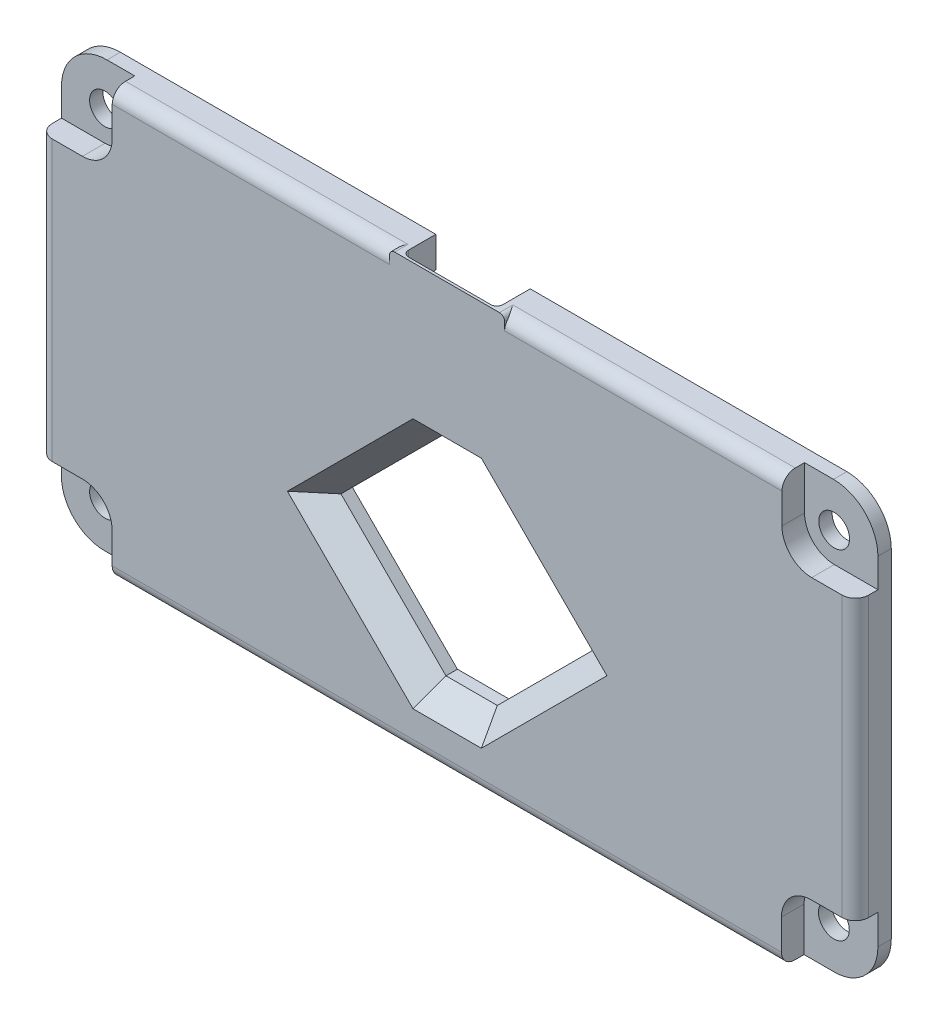
SolidWorks part; units mm, degrees
ref_plane "前视基准面" through (0, 0, 0) normal (0, 0, 1) x (1, 0, 0)
ref_plane "上视基准面" through (0, 0, 0) normal (0, 1, 0) x (1, 0, 0)
ref_plane "右视基准面" through (0, 0, 0) normal (1, 0, 0) x (0, 0, -1)
other "Configuration Table"
sketch "草图1" plane through (0, 0, 0) normal (0, 0, 1) x (1, 0, 0)
  line L0 (-73.6757, 40.1224) -> (-2.9366, 40.1224) construction
  line L1 (1.3873, 35.7985) -> (1.3873, 2.8575) construction
  line L2 (-2.8575, -1.3873) -> (-73.9297, -1.3873) construction
  line L3 (-78.111, 2.794) -> (-78.111, 35.6871) construction
  line L4 (-73.6757, 40.1224) -> (-43.4611, 40.1224)
  line L5 (1.3873, 35.7985) -> (1.3873, 2.8575)
  line L6 (-2.8575, -1.3873) -> (-73.9297, -1.3873)
  line L7 (-78.111, 2.794) -> (-78.111, 35.6871)
  line L8 (-38.3541, 24.0892) -> (-38.3541, 5.5516) construction
  line L9 (-6.6127, 15.1224) -> (-20.6127, 15.1224)
  line L10 (-6.6127, 15.1224) -> (-6.6127, 39.1224)
  line L11 (-6.6127, 39.1224) -> (-20.6127, 39.1224)
  line L12 (-20.6127, 15.1224) -> (-20.6127, 39.1224)
  line L13 (-56.111, 39.1224) -> (-70.111, 39.1224)
  line L14 (-56.111, 39.1224) -> (-56.111, 15.1224)
  line L15 (-56.111, 15.1224) -> (-70.111, 15.1224)
  line L16 (-70.111, 39.1224) -> (-70.111, 15.1224)
  line L17 (-38.2287, 24.0892) -> (-38.4795, 24.0892) construction
  line L18 (-38.6562, 5.5516) -> (-38.0519, 5.5516) construction
  line L19 (-47.9069, 14.732) -> (-28.8012, 14.732) construction
  line L20 (-47.9069, 14.6067) -> (-47.9069, 14.8574) construction
  line L21 (-28.8012, 14.8574) -> (-28.8012, 14.6067) construction
  line L22 (-38.3541, 14.732) -> (-44.9692, 8.1169) construction
  line L23 (-44.9692, 8.1169) -> (-48.3162, 4.7699) construction
  line L24 (-38.3541, 27.46) -> (-51.082, 14.732)
  line L25 (-38.3541, 27.46) -> (-25.6262, 14.732)
  line L26 (-51.082, 14.732) -> (-38.3541, 2.0041)
  line L27 (-25.6262, 14.732) -> (-38.3541, 2.0041)
  line L28 (-38.3541, 27.46) -> (-38.3541, 2.0041) construction
  line L29 (-51.082, 14.732) -> (-25.6262, 14.732) construction
  line L30 (-42.9611, 38.7041) -> (-42.9611, 36.9452) construction
  line L32 (-43.4611, 40.1224) -> (-43.4611, 30.1224)
  line L33 (-43.4611, 30.1224) -> (-33.2671, 30.1224)
  line L34 (-33.2671, 40.1224) -> (-33.2671, 30.1224)
  line L35 (-33.7671, 36.9452) -> (-33.7671, 38.7041) construction
  line L36 (-33.2671, 40.1224) -> (-2.9366, 40.1224)
  circle A0 centre (-73.8718, 35.8941) radius 1.5 construction
  circle A1 centre (-73.8718, 35.8941) radius 1.5
  circle A2 centre (-73.8718, 2.882) radius 1.5 construction
  circle A3 centre (-73.8718, 2.882) radius 1.5
  circle A4 centre (-2.9024, 2.882) radius 1.5 construction
  circle A5 centre (-2.9024, 2.882) radius 1.5
  circle A6 centre (-2.8731, 35.8776) radius 1.5 construction
  circle A7 centre (-2.8731, 35.8776) radius 1.5
  arc A8 (1.3873, 35.7985) -> (-2.9366, 40.1224) centre (-2.9366, 35.7985) ccw construction
  arc A9 (-2.8575, -1.3873) -> (1.3873, 2.8575) centre (-2.8575, 2.8575) ccw construction
  arc A10 (-78.111, 2.794) -> (-73.9297, -1.3873) centre (-73.9297, 2.794) ccw construction
  arc A11 (-73.6757, 40.1224) -> (-78.111, 35.6871) centre (-73.6757, 35.6871) ccw construction
  arc A12 (1.3873, 35.7985) -> (-2.9366, 40.1224) centre (-2.9366, 35.7985) ccw
  arc A13 (-2.8575, -1.3873) -> (1.3873, 2.8575) centre (-2.8575, 2.8575) ccw
  arc A14 (-78.111, 2.794) -> (-73.9297, -1.3873) centre (-73.9297, 2.794) ccw
  arc A15 (-73.6757, 40.1224) -> (-78.111, 35.6871) centre (-73.6757, 35.6871) ccw
  dimension "D1" = 8
  dimension "D2" = 8
  dimension "D3" = 1
  dimension "D4" = 1
  dimension "D5" = 14
  dimension "D6" = 14
  dimension "D7" = 24
  dimension "D8" = 18
  dimension "D9" = 18
  dimension "D10" = 0.5
  dimension "D11" = 0.5
  dimension "D12" = 10
extrude "凸台-拉伸1" add sketch "草图1" along normal blind 3.5
sketch "草图2" plane through (0, 0, 3.5) normal (0, 0, 1) x (1, 0, 0)
  line L1 (-20.6127, 39.1224) -> (-6.6127, 39.1224)
  line L2 (-20.6127, 39.1224) -> (-20.6127, 15.1224)
  line L3 (-20.6127, 15.1224) -> (-6.6127, 15.1224)
  line L4 (-6.6127, 39.1224) -> (-6.6127, 15.1224)
  line L5 (-70.111, 39.1224) -> (-56.111, 39.1224)
  line L6 (-70.111, 39.1224) -> (-70.111, 15.1224)
  line L7 (-70.111, 15.1224) -> (-56.111, 15.1224)
  line L8 (-56.111, 39.1224) -> (-56.111, 15.1224)
extrude "凸台-拉伸2" add sketch "草图2" against normal blind 0.5
sketch "草图3" plane through (0, 0, 3.5) normal (0, 0, 1) x (1, 0, 0)
  line L0 (-38.3541, 27.46) -> (-40.8541, 24.96)
  line L1 (-38.3541, 27.46) -> (-51.082, 14.732) construction
  line L2 (-40.8541, 24.96) -> (-35.8541, 24.96)
  line L3 (-25.6262, 14.732) -> (-38.3541, 27.46) construction
  line L4 (-35.8541, 24.96) -> (-38.3541, 27.46)
  line L5 (-38.3541, 2.0041) -> (-40.8541, 4.5041)
  line L6 (-51.082, 14.732) -> (-38.3541, 2.0041) construction
  line L7 (-40.8541, 4.5041) -> (-35.8541, 4.5041)
  line L8 (-38.3541, 2.0041) -> (-25.6262, 14.732) construction
  line L9 (-35.8541, 4.5041) -> (-38.3541, 2.0041)
  dimension "D1" = 2.5
  dimension "D2" = 45
  dimension "D3" = 2.5
extrude "凸台-拉伸3" add sketch "草图3" against normal blind 3.5
chamfer "倒角2" distance 2 angle 50 6 edges at (-30.7401, 9.6181, 3.5) (-38.3541, 4.5041, 3.5) (-45.968, 9.6181, 3.5) (-30.7401, 19.846, 3.5) (-38.3541, 24.96, 3.5) (-45.968, 19.846, 3.5) first distance on face at (-1.4024, 2.882, 3.5)
sketch "草图4" plane through (0, 30.1224, 0) normal (0, 1, 0) x (1, 0, 0)
  line L0 (-33.2671, -0.5) -> (-33.7671, -0.5)
  line L1 (-33.2671, -3.5) -> (-33.2671, 0) construction
  line L2 (-33.7671, -0.5) -> (-33.7671, -2.6525)
  line L3 (-34.3646, -3.25) -> (-42.3636, -3.25)
  line L4 (-42.9611, -2.6525) -> (-42.9611, -0.5)
  line L5 (-42.9611, -0.5) -> (-43.4611, -0.5)
  line L6 (-43.4611, -3.5) -> (-43.4611, 0) construction
  line L7 (-43.4611, -0.5) -> (-43.4611, -3.5)
  line L8 (-43.4611, -3.5) -> (-33.2671, -3.5)
  line L9 (-33.2671, -3.5) -> (-33.2671, -0.5)
  arc A0 (-33.7671, -2.6525) -> (-34.3646, -3.25) centre (-34.3646, -2.6525) cw
  arc A1 (-42.3636, -3.25) -> (-42.9611, -2.6525) centre (-42.3636, -2.6525) cw
  dimension "D1" = 0.25
  dimension "D2" = 0.5
  dimension "D3" = 0.5
  dimension "D4" = 3
  dimension "D5" = 3
extrude "凸台-拉伸4" add sketch "草图4" along normal up to surface (10 mm away) up to face at (-18.1018, 40.1224, 1.75)
sketch "草图5" plane through (0, 0, 3.5) normal (0, 0, 1) x (1, 0, 0)
  line L0 (-70.9718, 35.8941) -> (-70.9718, 40.1224)
  line L1 (-2.9366, 40.1224) -> (-73.6757, 40.1224) construction
  line L2 (-73.8718, 32.9941) -> (-78.111, 32.9941)
  line L3 (-78.111, 35.6871) -> (-78.111, 2.794) construction
  line L4 (-73.8718, 5.782) -> (-78.111, 5.782)
  line L5 (-70.9718, 2.882) -> (-70.9718, -1.3873)
  line L6 (-70.9718, 40.1224) -> (-73.6757, 40.1224)
  line L7 (-78.111, 32.9941) -> (-78.111, 35.6871)
  line L8 (-5.8024, 2.882) -> (-5.8024, -1.3873)
  line L9 (-73.9297, -1.3873) -> (-2.8575, -1.3873) construction
  line L10 (-2.9024, 5.782) -> (1.3873, 5.782)
  line L11 (-5.7575, 40.1224) -> (-2.9366, 40.1224)
  line L12 (1.3873, 32.9776) -> (1.3873, 35.7985)
  line L13 (-2.8575, 32.9776) -> (1.3873, 32.9776)
  line L14 (1.3873, 2.8575) -> (1.3873, 35.7985) construction
  line L15 (-5.7575, 35.8776) -> (-5.7575, 40.1224)
  line L16 (1.3873, 5.782) -> (1.3873, 2.8575)
  line L17 (-5.8024, -1.3873) -> (-2.8575, -1.3873)
  line L18 (-70.9718, -1.3873) -> (-73.9297, -1.3873)
  line L19 (-78.111, 5.782) -> (-78.111, 2.794)
  arc A0 (-73.8718, 32.9941) -> (-70.9718, 35.8941) centre (-73.8718, 35.8941) ccw
  arc A1 (-70.9718, 2.882) -> (-73.8718, 5.782) centre (-73.8718, 2.882) ccw
  arc A2 (-2.9024, 5.782) -> (-5.8024, 2.882) centre (-2.9024, 2.882) ccw
  arc A3 (-5.7575, 35.8776) -> (-2.8575, 32.9776) centre (-2.8575, 35.8776) ccw
  arc A4 (-73.6757, 40.1224) -> (-78.111, 35.6871) centre (-73.6757, 35.6871) ccw construction
  arc A5 (-73.6757, 40.1224) -> (-78.111, 35.6871) centre (-73.6757, 35.6871) ccw
  circle A6 centre (-73.8718, 35.8941) radius 1.5 construction
  circle A7 centre (-73.8718, 35.8941) radius 1.5
  arc A8 (1.3873, 35.7985) -> (-2.9366, 40.1224) centre (-2.9366, 35.7985) ccw construction
  arc A9 (1.3873, 35.7985) -> (-2.9366, 40.1224) centre (-2.9366, 35.7985) ccw
  circle A10 centre (-2.8731, 35.8776) radius 1.5 construction
  circle A11 centre (-2.8731, 35.8776) radius 1.5
  arc A12 (-2.8575, -1.3873) -> (1.3873, 2.8575) centre (-2.8575, 2.8575) ccw construction
  arc A13 (-2.8575, -1.3873) -> (1.3873, 2.8575) centre (-2.8575, 2.8575) ccw
  circle A14 centre (-2.9024, 2.882) radius 1.5 construction
  circle A15 centre (-2.9024, 2.882) radius 1.5
  arc A16 (-78.111, 2.794) -> (-73.9297, -1.3873) centre (-73.9297, 2.794) ccw construction
  arc A17 (-78.111, 2.794) -> (-73.9297, -1.3873) centre (-73.9297, 2.794) ccw
  circle A18 centre (-73.8718, 2.882) radius 1.5 construction
  circle A19 centre (-73.8718, 2.882) radius 1.5
  dimension "D1" = 5.8
  dimension "D2" = 5.8
  dimension "D3" = 5.8
  dimension "D4" = 5.8
extrude "切除-拉伸1" cut sketch "草图5" against normal blind 2.2
fillet "圆角1" radius 1.3 3 edges at (1.3873, 19.3798, 3.5) (-78.111, 19.388, 3.5) (-38.3871, -1.3873, 3.5)
sketch "草图6" plane through (-5.7575, 0, 0) normal (1, 0, 0) x (0, 0, -1)
  line L0 (-1.3, 40.1224) -> (-3.5, 40.1224) construction
  line L2 (-3.5, 40.1224) -> (-3.5, 35.8776) construction
  line L3 (-2.2, 40.1224) -> (-3.5, 40.1224)
  line L4 (-3.5, 40.1224) -> (-3.5, 38.8224)
  arc A0 (-2.2, 40.1224) -> (-3.5, 38.8224) centre (-2.2, 38.8224) ccw
  dimension "D1" = 2.6
extrude "切除-拉伸2" cut sketch "草图6" against normal blind 27
sketch "草图7" plane through (-70.9718, 0, 0) normal (-1, 0, 0) x (0, 0, 1)
  line L0 (2.2, 40.1224) -> (3.5, 40.1224)
  line L1 (3.5, 40.1224) -> (3.5, 38.8224)
  line L2 (3.5, 35.8941) -> (3.5, 40.1224) construction
  line L3 (1.3, 40.1224) -> (3.5, 40.1224) construction
  arc A0 (3.5, 38.8224) -> (2.2, 40.1224) centre (2.2, 38.8224) ccw
  dimension "D1" = 1.3
extrude "切除-拉伸3" cut sketch "草图7" against normal blind 27
fillet "圆角2" radius 0.5 2 edges at (-43.9718, 40.1224, 2.85) (-32.7575, 40.1224, 2.85)
sketch "草图8" plane through (0, 0, 0.5) normal (0, 0, -1) x (-1, 0, 0)
  line L0 (33.7671, 40.1224) -> (33.7671, 30.1224) construction
  line L1 (33.2671, 40.1224) -> (33.7671, 40.1224)
  line L2 (33.2671, 40.1224) -> (33.2671, 37.1224)
  line L3 (33.2671, 37.1224) -> (33.7671, 37.1224)
  line L4 (33.7671, 40.1224) -> (33.7671, 37.1224)
  line L5 (42.9611, 40.1224) -> (42.9611, 30.1224) construction
  line L6 (43.4611, 40.1224) -> (42.9611, 40.1224)
  line L7 (43.4611, 40.1224) -> (43.4611, 37.1224)
  line L8 (43.4611, 37.1224) -> (42.9611, 37.1224)
  line L9 (42.9611, 40.1224) -> (42.9611, 37.1224)
  dimension "D1" = 3
extrude "凸台-拉伸5" add sketch "草图8" along normal up to surface (0.5 mm away) up to face at (-63.111, 27.1224, 0)
sketch "草图9" plane through (0, 0, 0) normal (0, 0, -1) x (-1, 0, 0)
  line L0 (42.9611, 40.1224) -> (73.6757, 40.1224) construction
  line L1 (31.9686, 36.9224) -> (45.0882, 36.9224)
  line L2 (31.9686, 36.9224) -> (31.9686, 34.9224)
  line L3 (31.9686, 34.9224) -> (45.0882, 34.9224)
  line L4 (45.0882, 36.9224) -> (45.0882, 34.9224)
  line L5 (31.9686, 32.9224) -> (45.0882, 32.9224)
  line L6 (31.9686, 32.9224) -> (31.9686, 30.9224)
  line L7 (31.9686, 30.9224) -> (45.0882, 30.9224)
  line L8 (45.0882, 32.9224) -> (45.0882, 30.9224)
  dimension "D1" = 2
  dimension "D2" = 3.2
  dimension "D3" = 2
  dimension "D4" = 2
extrude "切除-拉伸4" cut sketch "草图9" against normal up to surface (0.5 mm away) up to face at (-33.5171, 33.6224, 0.5)
